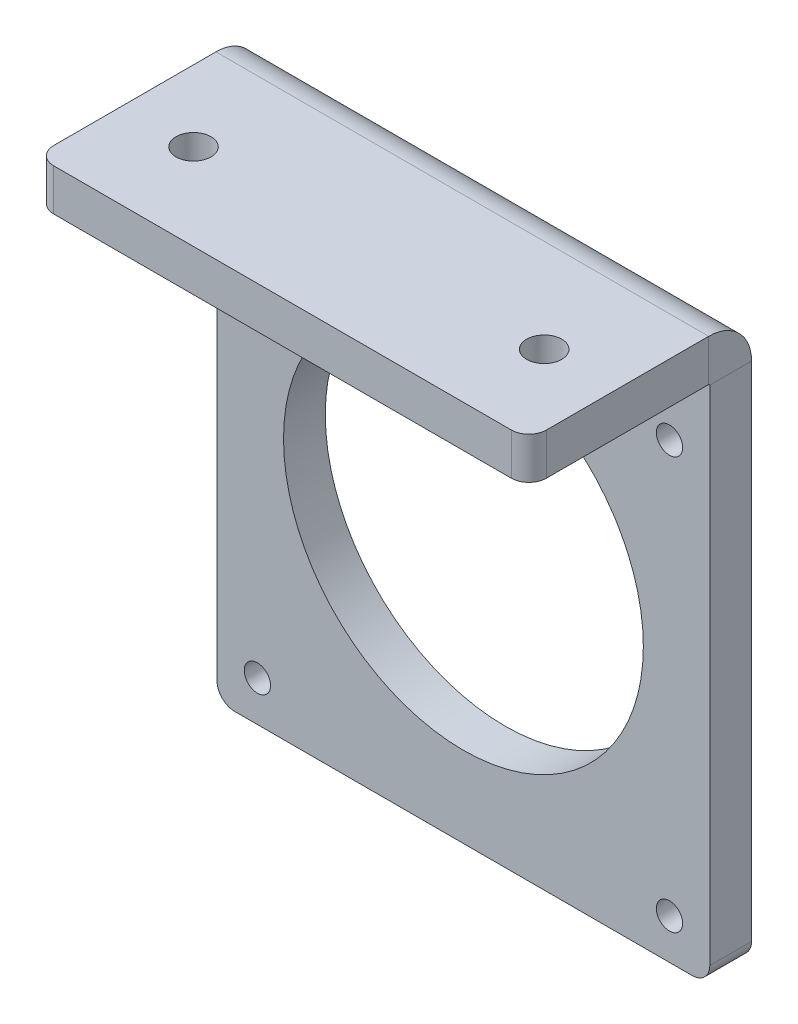
SolidWorks part; units mm, degrees
note: The reader was unsure of these and kept them because the rebuilt part matched: flange length of "Edge-Flange1".
ref_plane "Front Plane" through (0, 0, 0) normal (0, 0, 1) x (1, 0, 0)
ref_plane "Top Plane" through (0, 0, 0) normal (0, 1, 0) x (1, 0, 0)
ref_plane "Right Plane" through (0, 0, 0) normal (1, 0, 0) x (0, 0, -1)
sketch "Sketch1" plane through (0, 0, 0) normal (0, 0, 1) x (1, 0, 0)
  line L1 (-28.1, 29.725) -> (28.1, 29.725)
  line L2 (-28.1, 29.725) -> (-28.1, -29.725)
  line L3 (-28.1, -29.725) -> (28.1, -29.725)
  line L4 (28.1, 29.725) -> (28.1, -29.725)
  line L5 (-28.1, 29.725) -> (28.1, -29.725) construction
  line L6 (-28.1, -29.725) -> (28.1, 29.725) construction
  circle A0 centre (0, 0) radius 20.52
  circle A1 centre (-23.5, 21.875) radius 1.5
  circle A2 centre (23.5, 21.875) radius 1.5
  circle A3 centre (-23.5, -25.125) radius 1.5
  circle A4 centre (23.5, -25.125) radius 1.5
  point P0 (0, 0)
  dimension "D3" = 41.04
  dimension "D6" = 3
  dimension "D1" = 56.2
  dimension "D2" = 59.45
  dimension "D4" = 7.85
  dimension "D5" = 4.6
  dimension "D7" = 4.6
  dimension "D8" = 4.6
base flange "Base-Flange1" sketch "Sketch1" thickness 4.7625 reverse thickness direction no parameters "D1"=0.7366
sketch "Sketch7" plane through (0, 29.725, 0) normal (0, 1, 0) x (1, 0, 0)
  line L1 (-28.1, 0) -> (28.1, 0)
  line L2 (-28.1, 0) -> (-28.1, -20.6375)
  line L3 (-28.1, -20.6375) -> (28.1, -20.6375)
  line L4 (28.1, 0) -> (28.1, -20.6375)
  dimension "D1" = 20.6375
  dimension "D2" = 56.2
edge flange "Edge-Flange1" sketch "Sketch10" flange angle 90 flange length 25.4 flange position material outside bend radius 0.127 thickness 4.7625 relief rectangular parameters "D6"=10
sketch "Sketch10" plane through (0, 29.725, 0) normal (0, 1, 0) x (-1, 0, 0)
  line L2 (-28.1, 0) -> (-28.1, 20.6375)
  line L3 (-28.1, 20.6375) -> (28.1, 20.6375)
  line L4 (28.1, 20.6375) -> (28.1, 0)
  line L7 (-28.1, 0) -> (28.1, 0) construction
  line L8 (-28.1, 0) -> (28.1, 0)
bend "EdgeBend1" bend radius 0.127 bend angle 90 parameters "D5"=1
fillet "Fillet1" radius 2 4 edges at (28.1, 32.1063, 20.6375) (-28.1, 32.1063, 20.6375) (-28.1, -29.725, -2.3813) (28.1, -29.725, -2.3813)
sketch "Sketch11" plane through (0, 34.4875, 0) normal (0, 1, 0) x (1, 0, 0)
  line L0 (-28.1, -10.7875) -> (28.1, -10.7875) construction
  line L1 (-28.1, -0.127) -> (-28.1, -18.6375) construction
  line L2 (28.1, -18.6375) -> (28.1, -0.127) construction
  line L3 (-26.1, -20.6375) -> (26.1, -20.6375) construction
  circle A0 centre (-20, -10.7875) radius 2
  circle A1 centre (20, -10.7875) radius 2
  dimension "D4" = 4
  dimension "D1" = 9.85
  dimension "D2" = 8.1
  dimension "D3" = 8.1
extrude "Cut-Extrude1" cut sketch "Sketch11" against normal up to next normal cut yes
sketch "Bend-Lines1" [suppressed] plane through (0, 0, 0) normal (0, 1, 0) x (1, 0, 0)
sketch "Bounding-Box1" [suppressed] plane through (0, 0, 0) normal (0, 1, 0) x (1, 0, 0)
sheet metal parameters "Sheet-Metal1" thickness 4.7625 parameters "D1"=0.7366
flat pattern "Flat-Pattern1" [suppressed]
sketch "Bend-Lines2" plane through (0, 0, 0) normal (0, 1, 0) x (1, 0, 0)
sketch3d "Bounding-Box2" [suppressed]
  line L0 (-28.1, 29.725, 0) -> (-28.1, -29.725, 0) construction
  line L1 (28.1, 29.725, 0) -> (28.1, -29.725, 0) construction
  line L2 (-28.1, 29.725, 0) -> (28.1, 29.725, 0) construction
  line L3 (-28.1, -29.725, 0) -> (28.1, -29.725, 0) construction
sheet metal parameters "Sheet-Metal2" thickness 4.7625 parameters "D1"=0.7366
flat pattern "Flat-Pattern1"
sketch "Bend-Lines2" plane through (0, 0, 0) normal (0, 0, 1) x (1, 0, 0)
  line L0 (28.1, 26.8055) -> (-28.1, 26.8055) construction
  line L1 (28.1, 26.8055) -> (-28.1, 26.8055) construction
sketch3d "Bounding-Box2" [suppressed]
  line L0 (28.1, -29.725, 0) -> (28.1, 49.2859, 0) construction
  line L1 (-28.1, -29.725, 0) -> (-28.1, 49.286, 0) construction
  line L2 (28.1, -29.725, 0) -> (-28.1, -29.725, 0) construction
  line L3 (28.1, 49.2859, 0) -> (-28.1, 49.286, 0) construction
bend of the flat pattern "Flatten-<EdgeBend1>1"
sheet metal parameters "Sheet-Metal3" thickness 4.7625 parameters "D1"=0.7366
flat pattern "Flat-Pattern1"
sketch "Bend-Lines2" plane through (0, 0, 0) normal (0, 0, 1) x (1, 0, 0)
  line L0 (28.1, 31.568) -> (-28.1, 31.568) construction
  line L1 (28.1, 31.568) -> (-28.1, 31.568) construction
sketch3d "Bounding-Box2" [suppressed]
  line L0 (28.1, -29.725, 0) -> (28.1, 54.0484, 0) construction
  line L1 (-28.1, -29.725, 0) -> (-28.1, 54.0485, 0) construction
  line L2 (28.1, -29.725, 0) -> (-28.1, -29.725, 0) construction
  line L3 (28.1, 54.0484, 0) -> (-28.1, 54.0485, 0) construction
bend of the flat pattern "Flatten-<EdgeBend1>1"
